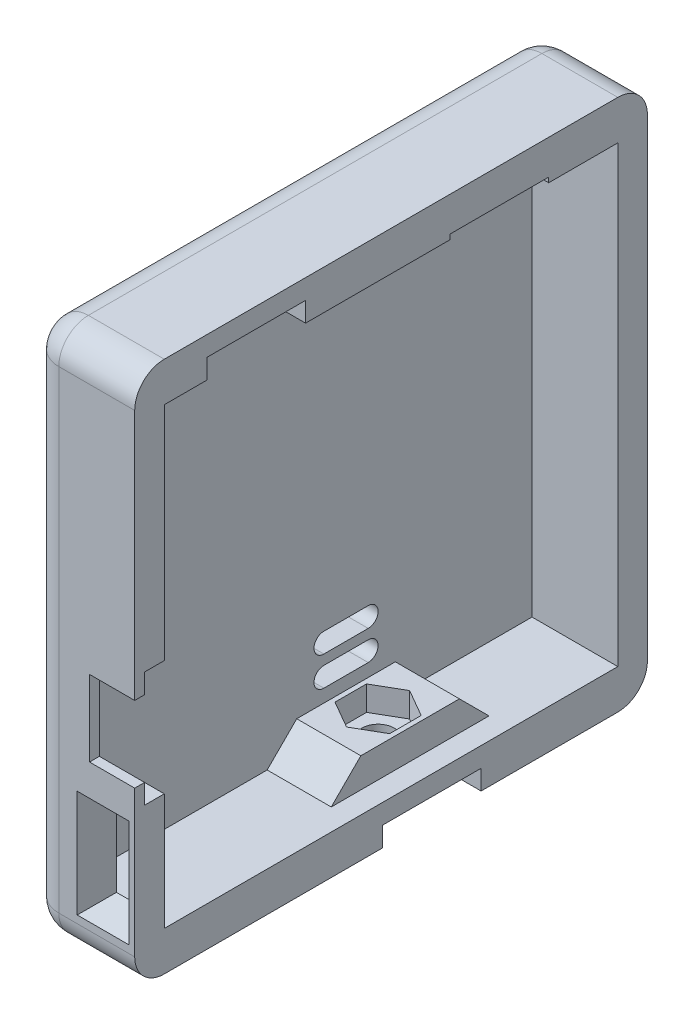
SolidWorks part; units mm, degrees
ref_plane "Alzado" through (0, 0, 0) normal (0, 0, 1) x (1, 0, 0)
ref_plane "Planta" through (0, 0, 0) normal (0, 1, 0) x (1, 0, 0)
ref_plane "Vista lateral" through (0, 0, 0) normal (1, 0, 0) x (0, 0, -1)
sketch "Croquis1" plane through (0, 0, 0) normal (0, 0, 1) x (1, 0, 0)
  line L0 (47.1448, -23.0661) -> (38.1448, -23.0661) construction
  line L1 (47.1448, 21.9339) -> (38.1448, 21.9339)
  line L2 (38.1448, 21.9339) -> (38.1448, -23.0661)
  line L3 (38.1448, -23.0661) -> (47.1448, -23.0661)
  line L5 (43.9571, -22.4046) -> (43.9571, -22.7804) construction
  line L6 (43.9571, -14.4275) -> (43.9571, -13.9275) construction
  line L7 (42.8182, -18.4161) -> (42.3182, -18.4161) construction
  line L8 (42.5648, -9.7411) -> (47.1448, -9.7411)
  line L9 (45.5648, -22.7804) -> (42.3182, -22.7804)
  line L10 (45.5648, -22.7804) -> (45.5648, -13.9275)
  line L11 (45.5648, -13.9275) -> (42.3182, -13.9275)
  line L12 (42.3182, -22.7804) -> (42.3182, -13.9275)
  line L14 (42.5648, -9.7411) -> (42.5648, -2.0411)
  line L21 (47.1448, -2.0411) -> (42.5648, -2.0411)
  line L22 (47.1448, -23.0661) -> (47.1448, -9.7411)
  line L23 (47.1448, 21.9339) -> (47.1448, -2.0411)
  dimension "D1" = 38.1448
  dimension "D2" = 42.3182
  dimension "D3" = 42.5648
  dimension "D4" = 43.9571
  dimension "D5" = 45.5648
  dimension "D6" = 47.1448
  dimension "D7" = 21.9339
  dimension "D8" = 2.0411
  dimension "D9" = 9.7411
  dimension "D10" = 13.9275
  dimension "D11" = 18.4161
  dimension "D12" = 22.7804
  dimension "D13" = 23.0661
extrude "Saliente-Extruir1" add sketch "Croquis1" along normal blind 2
sketch "Croquis5" plane through (0, 0, 2) normal (0, 0, 1) x (1, 0, 0)
  line L0 (47.1448, -23.0661) -> (47.1448, -23.5661) construction
  line L1 (38.1448, -23.0661) -> (47.1448, -23.0661) construction
  line L2 (38.1448, 21.9339) -> (38.1448, -23.0661) construction
  line L3 (38.1448, -23.0661) -> (47.1448, -23.0661)
  line L4 (38.1448, -23.0661) -> (38.1448, -23.5661)
  line L5 (38.1448, -23.5661) -> (47.1448, -23.5661)
  line L6 (47.1448, -23.0661) -> (47.1448, -23.5661)
  line L7 (47.1448, -2.0411) -> (47.1448, 21.9339) construction
  line L8 (47.1448, 21.9339) -> (38.1448, 21.9339)
  line L9 (47.1448, 21.9339) -> (47.1448, 22.4339)
  line L10 (47.1448, 22.4339) -> (38.1448, 22.4339)
  line L11 (38.1448, 21.9339) -> (38.1448, 22.4339)
  line L12 (47.1448, 21.9339) -> (38.1448, 21.9339) construction
  dimension "D1" = 0.5
extrude "Arreglo_impresion1" add sketch "Croquis5" against normal up to vertex (2 mm away)
sketch "Croquis6" plane through (0, -23.5661, 0) normal (0, -1, 0) x (1, 0, 0)
  line L0 (47.1448, -45) -> (47.1448, -46) construction
  line L1 (38.1448, 0) -> (38.1448, -4.4797) construction
  line L2 (38.1448, 0) -> (47.1448, 0) construction
  line L3 (38.1448, 2) -> (47.1448, 2) construction
  line L4 (47.1448, 2) -> (38.1448, 2)
  line L5 (47.1448, 2) -> (47.1448, -46)
  line L6 (47.1448, -46) -> (38.1448, -46)
  line L7 (38.1448, 2) -> (38.1448, -46)
  line L8 (38.1448, 0) -> (38.1448, 2) construction
  dimension "D1" = 48
extrude "Saliente-Extruir4" add sketch "Croquis6" along normal blind 2
sketch "Croquis7" plane through (0, 0, -46) normal (0, 0, -1) x (-1, 0, 0)
  line L0 (-38.1448, -25.5661) -> (-38.1448, -23.5661) construction
  line L1 (-38.1448, -25.5661) -> (-47.1448, -25.5661)
  line L2 (-38.1448, -25.5661) -> (-38.1448, 22.4339)
  line L3 (-38.1448, 22.4339) -> (-47.1448, 22.4339)
  line L4 (-47.1448, -25.5661) -> (-47.1448, 22.4339)
  line L5 (-47.1448, -2.0411) -> (-47.1448, 22.4339) construction
  line L6 (-47.1448, -25.5661) -> (-47.1448, -23.5661) construction
  line L7 (-38.1448, -23.5661) -> (-47.1448, -23.5661) construction
  dimension "D1" = 46
  dimension "D2" = 2
extrude "Saliente-Extruir5" add sketch "Croquis7" along normal blind 2
sketch "Croquis8" plane through (0, 22.4339, 0) normal (0, 1, 0) x (1, 0, 0)
  line L0 (47.1448, -2) -> (38.1448, -2) construction
  line L1 (38.1448, -2) -> (47.1448, -2)
  line L2 (38.1448, -2) -> (38.1448, 48)
  line L3 (38.1448, 48) -> (47.1448, 48)
  line L4 (47.1448, -2) -> (47.1448, 48)
  line L5 (38.1448, 0) -> (38.1448, -2) construction
  line L6 (38.1448, 48) -> (47.1448, 48) construction
  line L7 (47.1448, 0) -> (47.1448, -2) construction
extrude "Saliente-Extruir6" add sketch "Croquis8" along normal blind 2
sketch "Croquis9" plane through (38.1448, 0, 0) normal (-1, 0, 0) x (0, 0, 1)
  line L0 (-48, -25.5661) -> (-48, 24.4339) construction
  line L1 (-48, 24.4339) -> (2, 24.4339)
  line L2 (-48, 24.4339) -> (-48, -25.5661)
  line L3 (-48, -25.5661) -> (2, -25.5661)
  line L4 (2, 24.4339) -> (2, -25.5661)
  line L5 (-48, 24.4339) -> (2, 24.4339) construction
  line L6 (2, -25.5661) -> (-48, -25.5661) construction
  line L7 (-24.385, -18.7545) -> (-24.385, -23.5661) construction
  line L8 (0, -23.5661) -> (-46, -23.5661) construction
  line L9 (-24.385, -18.7545) -> (-24.885, -18.7545) construction
  line L10 (-24.885, -18.7545) -> (-24.885, -19.2545) construction
  line L11 (-24.885, -17.2545) -> (-24.885, -16.2545) construction
  line L12 (-24.885, -19.2545) -> (-29.385, -19.2545) construction
  line L13 (-24.885, -19.2545) -> (-24.885, -17.2545) construction
  line L14 (-24.885, -17.2545) -> (-29.385, -17.2545) construction
  line L15 (-29.385, -19.2545) -> (-29.385, -17.2545) construction
  line L16 (-29.385, -15.2545) -> (-24.885, -15.2545) construction
  line L21 (-29.385, -14.2545) -> (-24.885, -14.2545)
  line L22 (-29.385, -16.2545) -> (-24.885, -16.2545)
  line L23 (-29.385, -18.2545) -> (-24.885, -18.2545) construction
  line L24 (-29.385, -17.2545) -> (-24.885, -17.2545)
  line L25 (-29.385, -19.2545) -> (-24.885, -19.2545)
  line L26 (2, 24.4339) -> (2, -25.5661) construction
  arc A0 (-29.385, -14.2545) -> (-29.385, -16.2545) centre (-29.385, -15.2545) ccw
  arc A1 (-24.885, -16.2545) -> (-24.885, -14.2545) centre (-24.885, -15.2545) ccw
  arc A2 (-29.385, -17.2545) -> (-29.385, -19.2545) centre (-29.385, -18.2545) ccw
  arc A3 (-24.885, -19.2545) -> (-24.885, -17.2545) centre (-24.885, -18.2545) ccw
  point P22 (-27.135, -18.2545)
  point P25 (-27.135, -15.2545)
  dimension "D1" = 1
  dimension "D2" = 29.135
  dimension "D3" = 10.3116
extrude "Saliente-Extruir7" add sketch "Croquis9" along normal blind 1.7 and the other way blind 0.3
sketch "Croquis10" plane through (47.1448, 0, 0) normal (1, 0, 0) x (0, 0, -1)
  line L0 (0, 22.4339) -> (46, 22.4339) construction
  line L1 (28.9915, 22.4339) -> (38.9915, 22.4339)
  line L2 (28.9915, 22.4339) -> (28.9915, 22.9339)
  line L3 (28.9915, 22.9339) -> (38.9915, 22.9339)
  line L4 (38.9915, 22.4339) -> (38.9915, 22.9339)
  line L5 (46, 22.4339) -> (46, -23.5661) construction
  line L6 (46, -23.5661) -> (0, -23.5661) construction
  dimension "D1" = 7.0085
  dimension "D2" = 46.5
extrude "Cortar-Extruir1" cut sketch "Croquis10" against normal up to vertex (8.7 mm away) up to point (38.4447, 22.4339, -46)
sketch "Croquis11" plane through (0, 0, 2) normal (0, 0, 1) x (1, 0, 0)
  line L0 (47.1448, 24.4339) -> (36.4448, 24.4339)
  line L1 (36.4448, 24.4339) -> (47.1448, 24.4339) construction
  line L2 (36.4448, 24.4339) -> (36.4448, -25.5661)
  line L3 (47.1448, -25.5661) -> (36.4448, -25.5661) construction
  line L4 (36.4448, -25.5661) -> (36.4448, 24.4339) construction
  line L5 (36.4448, -25.5661) -> (47.1448, -25.5661)
  line L6 (47.1448, -25.5661) -> (47.1448, -9.7411) construction
  line L7 (47.1448, -25.5661) -> (47.1448, -9.7411)
  line L8 (47.1448, -9.7411) -> (42.5648, -9.7411)
  line L9 (47.1448, -9.7411) -> (42.5648, -9.7411) construction
  line L10 (42.5648, -9.7411) -> (42.5648, -2.0411)
  line L11 (42.5648, -9.7411) -> (42.5648, -2.0411) construction
  line L12 (42.5648, -2.0411) -> (47.1448, -2.0411)
  line L13 (47.1448, -2.0411) -> (47.1448, 24.4339) construction
  line L14 (42.5648, -2.0411) -> (47.1448, -2.0411) construction
  line L15 (47.1448, -2.0411) -> (47.1448, 24.4339)
  line L16 (42.3182, -13.9275) -> (42.3182, -22.7804) construction
  line L17 (42.3182, -13.9275) -> (45.5648, -13.9275)
  line L18 (42.3182, -13.9275) -> (42.3182, -22.7804)
  line L19 (42.3182, -22.7804) -> (45.5648, -22.7804)
  line L20 (45.5648, -13.9275) -> (45.5648, -22.7804)
  line L21 (45.5648, -13.9275) -> (42.3182, -13.9275) construction
  dimension "D1" = 1.58
  dimension "D2" = 2.7857
extrude "Saliente-Extruir8" add sketch "Croquis11" along normal blind 1
sketch "Croquis12" plane through (0, -25.5661, 0) normal (0, -1, 0) x (1, 0, 0)
  line L0 (36.4448, 3) -> (47.1448, 3) construction
  line L1 (47.1448, 3) -> (36.4448, 3)
  line L2 (47.1448, 3) -> (47.1448, -48)
  line L3 (47.1448, -48) -> (36.4448, -48)
  line L4 (36.4448, 3) -> (36.4448, -48)
  line L5 (47.1448, -48) -> (47.1448, 3) construction
  line L6 (47.1448, -48) -> (36.4448, -48) construction
  line L7 (36.4448, -48) -> (36.4448, 3) construction
extrude "Saliente-Extruir9" add sketch "Croquis12" along normal blind 2
sketch "Croquis13" plane through (0, 0, -48) normal (0, 0, -1) x (-1, 0, 0)
  line L0 (-47.1448, 24.4339) -> (-47.1448, -27.5661) construction
  line L1 (-47.1448, 24.4339) -> (-36.4448, 24.4339)
  line L2 (-47.1448, 24.4339) -> (-47.1448, -27.5661)
  line L3 (-47.1448, -27.5661) -> (-36.4448, -27.5661)
  line L4 (-36.4448, 24.4339) -> (-36.4448, -27.5661)
  line L5 (-47.1448, 24.4339) -> (-36.4448, 24.4339) construction
  line L6 (-36.4448, -27.5661) -> (-47.1448, -27.5661) construction
  line L7 (-36.4448, 24.4339) -> (-36.4448, -27.5661) construction
extrude "Saliente-Extruir10" add sketch "Croquis13" along normal blind 1
sketch "Croquis14" plane through (0, 24.4339, 0) normal (0, 1, 0) x (1, 0, 0)
  line L0 (36.4448, 49) -> (47.1448, 49) construction
  line L1 (47.1448, 49) -> (36.4448, 49)
  line L2 (47.1448, 49) -> (47.1448, -3)
  line L3 (47.1448, -3) -> (36.4448, -3)
  line L4 (36.4448, 49) -> (36.4448, -3)
  line L5 (47.1448, -3) -> (47.1448, 49) construction
  line L6 (47.1448, -3) -> (36.4448, -3) construction
  line L7 (36.4448, -3) -> (36.4448, 49) construction
extrude "Saliente-Extruir11" add sketch "Croquis14" along normal blind 2
sketch "Croquis17" plane through (38.4448, 0, 0) normal (1, 0, 0) x (0, 0, -1)
  line L0 (46, -23.5661) -> (46, 22.4339) construction
  line L2 (46, -23.5661) -> (0, -23.5661) construction
  line L7 (22.135, -20.5661) -> (32.135, -20.5661)
  line L9 (0, -23.5661) -> (46, -23.5661) construction
  line L10 (22.135, -20.5661) -> (19.135, -23.5661)
  line L11 (32.135, -20.5661) -> (35.135, -23.5661)
  line L12 (19.135, -23.5661) -> (35.135, -23.5661)
  dimension "D1" = 10.865
  dimension "D2" = 3
  dimension "D3" = 23.865
extrude "Saliente-Extruir12" add sketch "Croquis17" along normal blind 6.5
sketch "Croquis19" plane through (0, -20.5661, 0) normal (0, 1, 0) x (1, 0, 0)
  line L0 (38.4448, 22.135) -> (44.9448, 32.135) construction
  line L1 (44.9448, 22.135) -> (38.4448, 22.135) construction
  line L2 (38.4448, 32.135) -> (38.4448, 22.135) construction
  line L3 (44.9448, 32.135) -> (38.4448, 32.135) construction
  circle A0 centre (41.6948, 27.135) radius 1.625
  dimension "D1" = 3.25
  dimension "D2" = 3.25
extrude "Cortar-Extruir2" cut sketch "Croquis19" against normal up to vertex
sketch "Croquis20" plane through (0, -20.5661, 0) normal (0, 1, 0) x (1, 0, 0)
  line L0 (38.4448, 32.135) -> (38.4448, 22.135) construction
  line L1 (41.6948, 30.335) -> (38.9235, 28.735)
  line L2 (38.9235, 28.735) -> (38.9235, 25.535)
  line L3 (38.9235, 25.535) -> (41.6948, 23.935)
  line L4 (41.6948, 23.935) -> (44.466, 25.535)
  line L5 (44.466, 25.535) -> (44.466, 28.735)
  line L6 (44.466, 28.735) -> (41.6948, 30.335)
  circle A0 centre (41.6948, 27.135) radius 2.7713 construction
  dimension "D1" = 5.5426
  dimension "D2" = 0.4787
  dimension "D3" = 1.8
extrude "Cortar-Extruir3" cut sketch "Croquis20" against normal blind 2.5
sketch "Croquis22" plane through (47.1448, 0, 0) normal (1, 0, 0) x (0, 0, -1)
  line L0 (22.135, -20.5661) -> (22.135, -27.5661) construction
  line L1 (32.135, -20.5661) -> (22.135, -20.5661) construction
  line L2 (49, -27.5661) -> (-3, -27.5661) construction
  line L4 (22.135, -27.5661) -> (32.135, -27.5661)
  line L5 (22.135, -27.5661) -> (22.135, -25.5661)
  line L6 (22.135, -25.5661) -> (32.135, -25.5661)
  line L7 (32.135, -27.5661) -> (32.135, -25.5661)
  line L12 (38.9915, 22.9339) -> (28.9915, 22.9339) construction
  line L13 (46, 22.4339) -> (46, -23.5661) construction
  line L14 (0, 22.4339) -> (28.9915, 22.4339) construction
  line L15 (4.3314, 22.4339) -> (14.3314, 22.4339)
  line L16 (4.3314, 22.4339) -> (4.3314, 24.4339)
  line L17 (4.3314, 24.4339) -> (14.3314, 24.4339)
  line L18 (14.3314, 22.4339) -> (14.3314, 24.4339)
  dimension "D1" = 13.865
  dimension "D2" = 23.865
  dimension "D3" = 48.5
  dimension "D4" = 31.6686
extrude "Cortar-Extruir4" cut sketch "Croquis22" against normal up to vertex (8.7 mm away)
sketch "Croquis23" plane through (47.1448, 0, 0) normal (1, 0, 0) x (0, 0, -1)
  line L0 (-3, -27.5661) -> (0, -27.5661)
  line L1 (22.135, -27.5661) -> (-3, -27.5661) construction
  line L2 (-3, -27.5661) -> (-3, -24.5661)
  line L3 (-3, -27.5661) -> (-3, -9.7411) construction
  line L4 (-3, 26.4339) -> (0, 26.4339)
  line L5 (-3, -2.0411) -> (-3, 26.4339) construction
  line L6 (-3, 26.4339) -> (49, 26.4339) construction
  line L7 (-3, 26.4339) -> (-3, 23.4339)
  line L8 (49, 26.4339) -> (49, 23.4339)
  line L9 (49, 26.4339) -> (49, -27.5661) construction
  line L10 (49, 26.4339) -> (46, 26.4339)
  line L11 (49, -27.5661) -> (46, -27.5661)
  line L12 (49, -27.5661) -> (32.135, -27.5661) construction
  line L13 (49, -27.5661) -> (49, -24.5661)
  arc A0 (-3, -24.5661) -> (0, -27.5661) centre (0, -24.5661) ccw
  arc A1 (-3, 23.4339) -> (0, 26.4339) centre (0, 23.4339) cw
  arc A2 (46, 26.4339) -> (49, 23.4339) centre (46, 23.4339) cw
  arc A3 (49, -24.5661) -> (46, -27.5661) centre (46, -24.5661) cw
  dimension "D1" = 3
extrude "Cortar-Extruir5" cut sketch "Croquis23" against normal up to vertex
fillet "Redondeo4" radius 3 8 edges at (36.4448, -26.6874, 2.1213) (36.4448, -0.5661, 3) (36.4448, 25.5553, 2.1213) (36.4448, 26.4339, -23) (36.4448, 25.5553, -48.1213) (36.4448, -0.5661, -49) (36.4448, -26.6874, -48.1213) (36.4448, -27.5661, -23)
sketch "Croquis24" plane through (0, 0, 3) normal (0, 0, 1) x (1, 0, 0)
  line L0 (45.5648, -13.9275) -> (46.5648, -13.9275) construction
  line L1 (45.5648, -22.7804) -> (45.5648, -13.9275) construction
  line L2 (45.5648, -13.9275) -> (42.3182, -13.9275) construction
  line L3 (42.3182, -22.7975) -> (42.3182, -23.7975) construction
  line L4 (42.3182, -22.7975) -> (41.3182, -22.7975) construction
  line L5 (45.5648, -13.9275) -> (45.5648, -12.9275) construction
  line L6 (39.4448, 23.4339) -> (39.4448, -24.5661) construction
  line L7 (41.3182, -23.7975) -> (46.5648, -23.7975)
  line L8 (41.3182, -23.7975) -> (41.3182, -12.9275)
  line L9 (41.3182, -12.9275) -> (46.5648, -12.9275)
  line L10 (46.5648, -23.7975) -> (46.5648, -12.9275)
  line L11 (39.4448, 23.4339) -> (47.1448, 23.4339) construction
  dimension "D1" = 1.8734
  dimension "D2" = 2.8734
  dimension "D3" = 46.2315
extrude "Cortar-Extruir6" cut sketch "Croquis24" against normal up to vertex (3 mm away) draft 18
sketch "Croquis25" plane through (0, 0, 0) normal (0, 0, -1) x (-1, 0, 0)
  line L2 (-47.1448, -2.0411) -> (-47.1448, -0.0411) construction
  line L3 (-42.5648, -2.0411) -> (-47.1448, -2.0411) construction
  line L4 (-47.1448, -2.0411) -> (-47.1448, 22.4339) construction
  line L5 (-42.5648, -9.7411) -> (-40.5648, -9.7411) construction
  line L6 (-42.5648, -9.7411) -> (-42.5648, -2.0411) construction
  line L7 (-40.5648, -9.7411) -> (-40.5648, -11.7411) construction
  line L8 (-40.5648, -11.7411) -> (-47.1448, -11.7411)
  line L9 (-40.5648, -11.7411) -> (-40.5648, -0.0411)
  line L10 (-40.5648, -0.0411) -> (-47.1448, -0.0411)
  line L11 (-47.1448, -11.7411) -> (-47.1448, -0.0411)
extrude "Cortar-Extruir7" cut sketch "Croquis25" against normal blind 2
